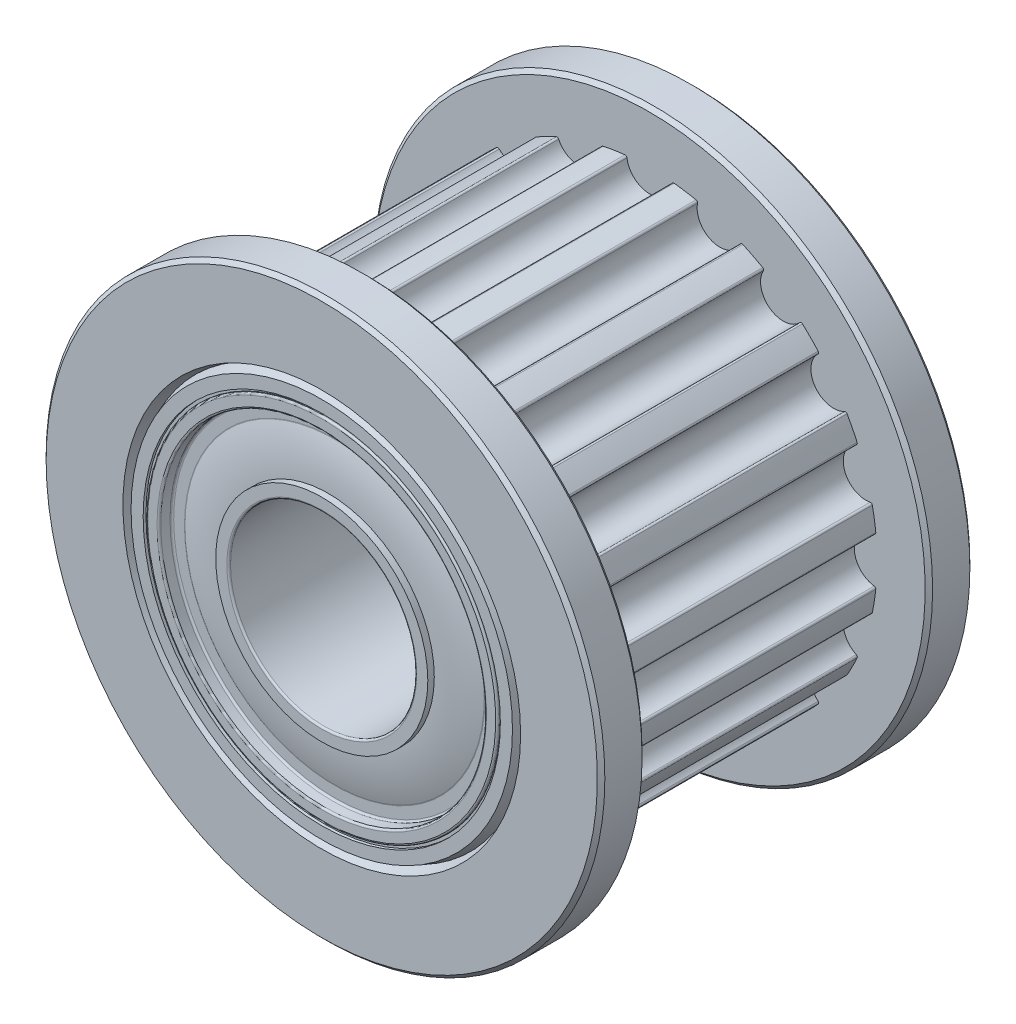
SolidWorks part; units mm, degrees
ref_plane "Front" through (0, 0, 0) normal (0, 0, 1) x (1, 0, 0)
ref_plane "Top" through (0, 0, 0) normal (0, 1, 0) x (1, 0, 0)
ref_plane "Right" through (0, 0, 0) normal (1, 0, 0) x (0, 0, -1)
sketch "Sketch1" plane through (0, 0, 0) normal (1, 0, 0) x (0, 0, -1)
  line L0 (-5, 0) -> (5, 0) construction
  line L1 (5, 7.5) -> (5, -7.5) construction
  line L2 (5, 7.5) -> (3.8, 7.5) construction
  line L3 (5, 2.5) -> (5, -2.5) construction
  line L4 (5, 6.11) -> (5, -6.11) construction
  line L5 (3, 0) -> (-3, 0) construction
  line L6 (3.8, 7.5) -> (3.8, 6.11) construction
  dimension "Width" = 10
  dimension "OD" = 15
  dimension "D3" = 1.2
  dimension "ID" = 5
  dimension "Diameter" = 12.22
  dimension "Max Belt Width" = 6
  dimension "Groove Depth" = 1.39
sketch "Sketch2" plane through (0, 0, 0) normal (1, 0, 0) x (0, 0, -1)
  line L0 (5, 2.5) -> (0, 2.5)
  line L1 (5, 2.5) -> (5, 2.8475)
  line L2 (5, 7.5) -> (5, -7.5) construction
  line L3 (5, 2.8475) -> (4.6525, 2.8475) construction
  line L4 (4.8263, 4.3725) -> (4.8263, 2.8475) construction
  line L5 (5, 4.72) -> (0, 4.72)
  line L6 (4.6525, 4.025) -> (4.6525, 4.3725)
  line L7 (5, 4.72) -> (5, 4.3725)
  line L8 (5, 4.3725) -> (4.6525, 4.3725)
  line L9 (4.6525, 4.3725) -> (4.6525, 2.8475) construction
  line L10 (0, 4.72) -> (0, 2.5)
  line L11 (4.8263, 2.8475) -> (5, 2.8475)
  arc A0 (4.6525, 4.025) -> (4.8263, 2.8475) centre (0.7494, 2.8475) cw
  dimension "D1" = 1.39
  dimension "D2" = 0.3475
revolve "Revolve1" add sketch "Sketch2" angle 360 about L0
mirror "Mirror1" about plane through (0, 0, 0) normal (0, 0, 1) of bodies 108
sketch "Sketch3" plane through (0, 0, 0) normal (1, 0, 0) x (0, 0, -1)
  line L0 (3.8, 7.5) -> (5, 7.5)
  line L1 (5, 7.5) -> (5, 5.3384)
  line L2 (5, 7.5) -> (5, -7.5) construction
  line L3 (5, 5.3384) -> (4.7, 5.2292)
  line L4 (4.7, 5.2292) -> (5, 5.12)
  line L5 (5, 5.12) -> (5, 4.795)
  line L6 (4.925, 4.72) -> (4.925, 4.795)
  line L7 (5, 4.72) -> (-5, 4.72) construction
  line L8 (4.925, 4.795) -> (5, 4.795)
  line L9 (3.8, 7.5) -> (3.8, 6.11)
  line L10 (3.8, 6.11) -> (-3.8, 6.11)
  line L11 (0, 6.11) -> (0, 4.72) construction
  line L12 (-4.925, 4.72) -> (4.925, 4.72)
  line L13 (-3.8, 7.5) -> (-3.8, 6.11)
  line L14 (-4.925, 4.795) -> (-5, 4.795)
  line L15 (-4.925, 4.72) -> (-4.925, 4.795)
  line L16 (-5, 5.12) -> (-5, 4.795)
  line L17 (-4.7, 5.2292) -> (-5, 5.12)
  line L18 (-5, 5.3384) -> (-4.7, 5.2292)
  line L19 (-5, 7.5) -> (-5, 5.3384)
  line L20 (-3.8, 7.5) -> (-5, 7.5)
  line L21 (4.7, 5.2292) -> (5, 5.2292) construction
  line L22 (4.85, 5.2292) -> (4.85, 4.72) construction
  dimension "D1" = 40
  dimension "D2" = 0.3
  dimension "D3" = 0.075
  dimension "D4" = 0.4
revolve "Revolve2" add sketch "Sketch3" angle 360 about L0
sketch "Sketch4" plane through (0, 0, 0) normal (0, 0, 1) x (1, 0, 0)
  line L0 (-0.611, 6.11) -> (0.611, 6.11)
  line L1 (-0.611, 6.11) -> (-0.611, 5.554) construction
  line L2 (-0.611, 5.554) -> (0.611, 5.554) construction
  line L3 (0.611, 5.554) -> (0.611, 6.11) construction
  line L4 (0, 6.11) -> (0, 5.554) construction
  arc A0 (0.611, 6.11) -> (-0.611, 6.11) centre (0, 6.11) cw
  dimension "D1" = 0.556
  dimension "D3" = 1.222
extrude "Cut-Extrude1" cut sketch "Sketch4" against normal up to surface and the other way up to surface up to face at (6.11, 0, -3.8) other way up to face at (7.5, 0, 3.8)
fillet "Fillet1" radius 0.05 2 edges at (0.6102, 6.0794, 0) (-0.6102, 6.0794, 0)
pattern_circular "CirPattern3" count 20 over 360 about axis through (0, 0, -3.8) along (0, 0, 1) of "Cut-Extrude1", "Fillet1"
chamfer "Chamfer1" distance 0.1 angle 45 4 edges at (7.5, 0, -5) (7.5, 0, -3.8) (7.5, 0, 3.8) (7.5, 0, 5)
fillet "Fillet2" radius 0.05 10 edges at (4.025, 0, 4.6525) (4.3725, 0, 4.6525) (4.72, 0, 5) (4.3725, 0, 5) (2.5, 0, 5) (2.5, 0, -5) (4.72, 0, -5) (4.025, 0, -4.6525) (4.3725, 0, -5) (2.8475, 0, -5)
combine bodies "Combine1" operation type add bodies to combine 113 109
ref_axis "Center Axis 1" through (0, 0, -4.95) along (0, 0, 1)
ref_plane "Contact Plane 1" through (0, 0, -3) normal (0, 0, 1) x (1, 0, 0)
ref_plane "Contact Plane 2" through (0, 0, 3) normal (0, 0, 1) x (1, 0, 0)
equation "\"D1@Sketch4\"=\"Groove Depth@Sketch1\"/2.5"
equation "\"D3@Sketch4\"=\"Diameter@Sketch1\"/10"
equation "\"D2@Sketch3\"=\"D3@Sketch1\"/4"
equation "\"D1@Sketch2\"=(\"OD@Sketch1\"-\"Diameter@Sketch1\")/2"
equation "\"D2@Sketch2\"=\"D1@Sketch2\"/4"
equation "\"D3@Sketch3\"=\"D2@Sketch3\"/4"
equation "\"D4@Sketch3\"=\"D3@Sketch1\"/3"
